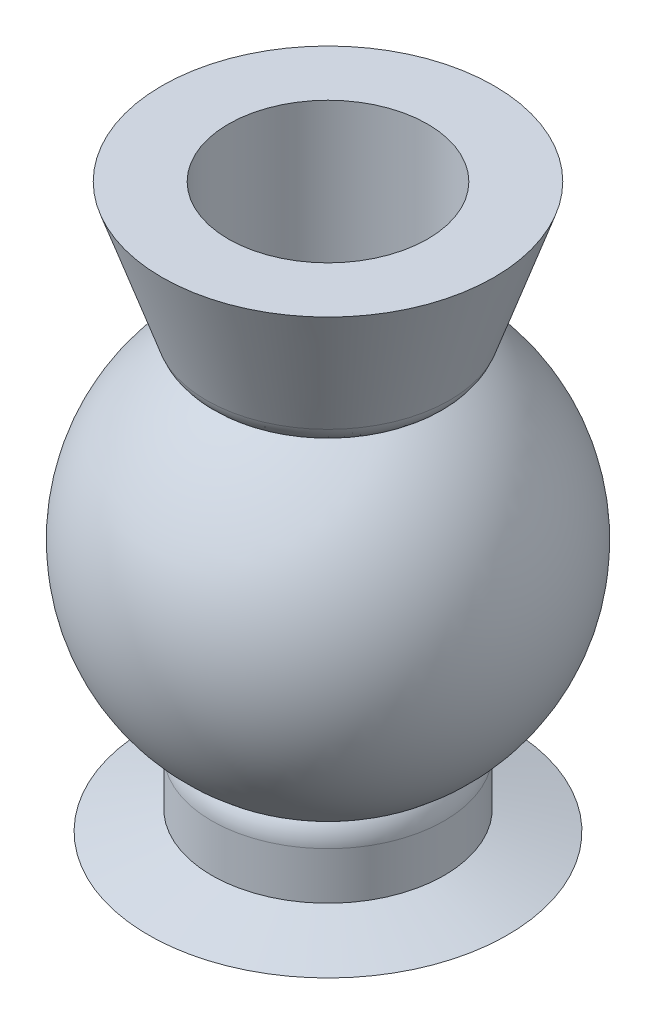
SolidWorks part; units mm, degrees
material "Alliage 1060"
ref_plane "Plan de face" through (0, 0, 0) normal (0, 0, 1) x (1, 0, 0)
ref_plane "Plan de dessus" through (0, 0, 0) normal (0, 1, 0) x (1, 0, 0)
ref_plane "Plan de droite" through (0, 0, 0) normal (1, 0, 0) x (0, 0, -1)
sketch "Esquisse1" plane through (0, 0, 0) normal (0, 0, 1) x (1, 0, 0)
  line L0 (0, 3) -> (0, -3) construction
  line L1 (0, -3) -> (0, 3)
  arc A0 (0, -3) -> (0, 3) centre (0, 0) ccw
  dimension "D1" = 3
revolve "Révolution1" add sketch "Esquisse1" angle 360 about L0
ref_plane "Plan1" through (0, 2.5, 0) normal (0, 1, 0) x (1, 0, 0)
sketch "Esquisse4" plane through (0, 0, 0) normal (0, 0, 1) x (1, 0, 0)
  line L0 (1.75, 2.5) -> (2.5, 4.6743)
  line L2 (2.5, 4.6743) -> (0, 4.6743)
  line L3 (3.3, 2.5) -> (-3.3, 2.5) construction
  line L4 (0, -3.6157) -> (0, 6.2678) construction
  line L5 (1.75, 2.5) -> (0, 2.5)
  line L6 (0, 2.5) -> (0, 4.6743)
  dimension "D1" = 1.75
  dimension "D2" = 2.5
  dimension "D3" = 2.3
revolve "Révolution2" add sketch "Esquisse4" angle 360 about L4
ref_plane "Plan2" through (0, -2.5, 0) normal (0, 1, 0) x (1, 0, 0)
sketch "Esquisse6" plane through (0, 0, 0) normal (0, 0, 1) x (1, 0, 0)
  line L0 (0, -2.5) -> (1.75, -2.5)
  line L1 (3.3, -2.5) -> (-3.3, -2.5) construction
  line L2 (1.75, -2.5) -> (1.75, -3.5)
  line L3 (1.75, -3.5) -> (2.7039, -3.8)
  line L4 (2.7039, -3.8) -> (0, -3.8)
  line L5 (0, -4.2412) -> (0, 4.9417) construction
  line L6 (0, -2.5) -> (0, -3.8)
  dimension "D1" = 1.75
  dimension "D2" = 1
  dimension "D3" = 0.3
  dimension "D4" = 1
revolve "Révolution3" add sketch "Esquisse6" angle 360 about L5
sketch "Esquisse5" plane through (0, 4.6743, 0) normal (0, 1, 0) x (1, 0, 0)
  circle A0 centre (0, 0) radius 1.5
  dimension "D1" = 3
extrude "Enlèv. mat.-Extru.2" cut sketch "Esquisse5" against normal through all
fillet "Congé2" radius 0.5 2 edges at (0, -2.5, -1.75) (0, 2.5, -1.75)
